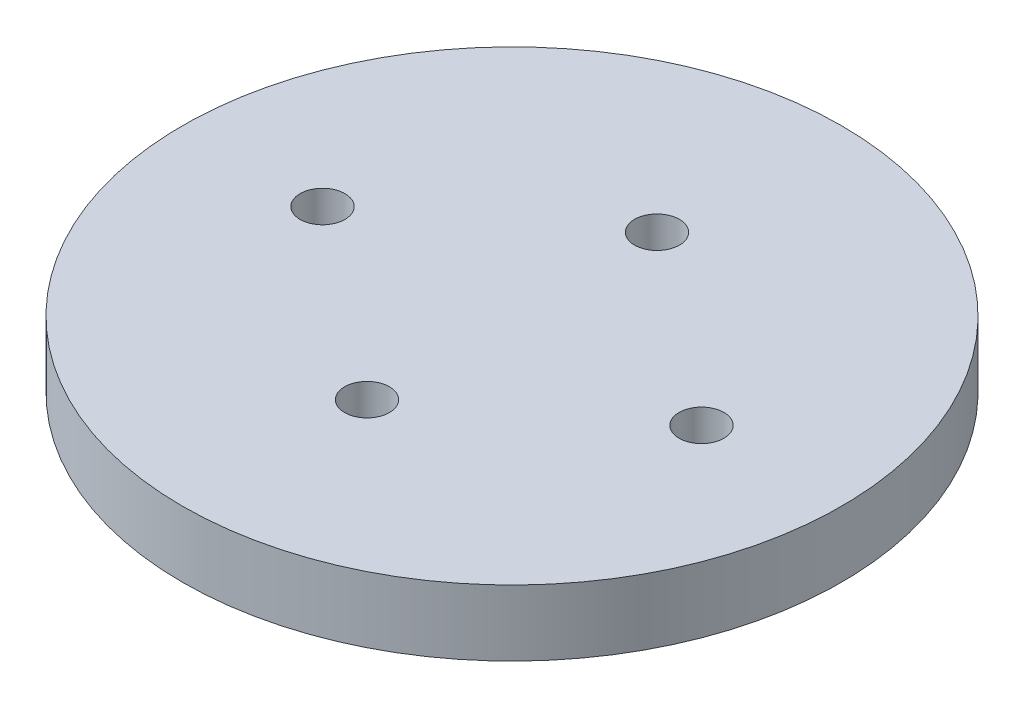
SolidWorks part; units mm, degrees
material "1060 Alloy"
ref_plane "Front Plane" through (0, 0, 0) normal (0, 0, 1) x (1, 0, 0)
ref_plane "Top Plane" through (0, 0, 0) normal (0, 1, 0) x (1, 0, 0)
ref_plane "Right Plane" through (0, 0, 0) normal (1, 0, 0) x (0, 0, -1)
sketch "Sketch1" plane through (0, 0, 0) normal (0, 1, 0) x (1, 0, 0)
  line L1 (57.825, 46.5) -> (-57.825, 46.5) construction
  line L2 (57.825, 46.5) -> (57.825, -46.5) construction
  line L3 (57.825, -46.5) -> (-57.825, -46.5) construction
  line L4 (-57.825, 46.5) -> (-57.825, -46.5) construction
  line L5 (-57.825, 46.5) -> (57.825, -46.5) construction
  line L6 (-57.825, 26.7384) -> (-42.825, 26.7384) construction
  line L36 (-42.825, 26.7384) -> (-9.5745, 0) construction
  line L37 (-9.5745, 0) -> (-42.825, -26.7384) construction
  line L38 (-42.825, -26.7384) -> (-57.825, -26.7384) construction
  line L39 (-57.825, -26.7384) -> (-57.825, -46.5) construction
  line L40 (-57.825, -46.5) -> (-33.2505, -46.5) construction
  line L41 (-33.2505, -46.5) -> (-33.2505, -34.4377) construction
  line L42 (-33.2505, -34.4377) -> (0, -7.6993) construction
  line L43 (0, -7.6993) -> (33.2505, -34.4377) construction
  line L44 (33.2505, -34.4377) -> (33.2505, -46.5) construction
  line L45 (33.2505, -46.5) -> (57.825, -46.5) construction
  line L46 (57.825, -46.5) -> (57.825, -26.7384) construction
  line L47 (57.825, -26.7384) -> (42.825, -26.7384) construction
  line L48 (42.825, -26.7384) -> (9.5745, 0) construction
  line L49 (9.5745, 0) -> (42.825, 26.7384) construction
  line L50 (42.825, 26.7384) -> (57.825, 26.7384) construction
  line L51 (57.825, 26.7384) -> (57.825, 46.5) construction
  line L52 (57.825, 46.5) -> (33.2505, 46.5) construction
  line L53 (33.2505, 46.5) -> (33.2505, 34.4377) construction
  line L54 (33.2505, 34.4377) -> (0, 7.6993) construction
  line L55 (0, 7.6993) -> (-33.2505, 34.4377) construction
  line L56 (-33.2505, 34.4377) -> (-33.2505, 46.5) construction
  line L57 (-33.2505, 46.5) -> (-57.825, 46.5) construction
  line L58 (-57.825, 46.5) -> (-57.825, 26.7384) construction
  line L59 (-57.825, -46.5) -> (57.825, 46.5) construction
  line L64 (42.825, 26.7384) -> (42.825, 34.4377)
  line L65 (42.825, 26.7384) -> (33.2505, 34.4377) construction
  line L66 (42.825, 34.4377) -> (33.2505, 34.4377)
  line L67 (33.2505, 34.4377) -> (-33.2505, 34.4377)
  line L68 (-33.2505, 34.4377) -> (-42.825, 34.4377)
  line L69 (-42.825, 34.4377) -> (-42.825, 26.7384)
  line L70 (-42.825, 26.7384) -> (-42.825, -26.7384)
  line L71 (-42.825, -26.7384) -> (-42.825, -34.4377)
  line L72 (-42.825, -34.4377) -> (-33.2505, -34.4377)
  line L73 (-33.2505, -34.4377) -> (33.2505, -34.4377)
  line L74 (33.2505, -34.4377) -> (42.825, -34.4377)
  line L75 (42.825, -34.4377) -> (42.825, -26.7384)
  line L78 (42.825, -26.7384) -> (42.825, 26.7384)
  line L79 (-9.5745, 0) -> (9.5745, 0) construction
  line L80 (0, 7.6993) -> (0, -7.6993) construction
  circle A1 centre (0, 11) radius 1.7
  circle A3 centre (-14.375, 0) radius 1.7
  circle A4 centre (0, 0) radius 25
  circle A5 centre (0, -11) radius 1.7
  circle A6 centre (14.375, 0) radius 1.7
  dimension "D6" = 3.4
  dimension "D8" = 3.4
  dimension "D9" = 50
  dimension "D1" = 115.65
  dimension "D2" = 93
  dimension "D3" = 12
  dimension "D4" = 15
  dimension "D10" = 11
  dimension "D5" = 28.75
extrude "Boss-Extrude1" add sketch "Sketch1" along normal blind 5 contours A4 A5 A1 A6 A3 region at (0, 0, 0)
equation "\"L1L\"=500"
equation "\"L1Thick\"=6.35"
equation "\"Harm-Drive-Outer\"=74.5"
equation "\"L1-Spacing\"=115.65"
equation "\"L-Bracket-HoleToWall\"=12.5"
equation "\"L-Bracket-HoleToSide\"=11"
equation "\"Bracket-Hole-D\"=6.8"
equation "\"D1@Sketch1\"=\"L1-Spacing\""
